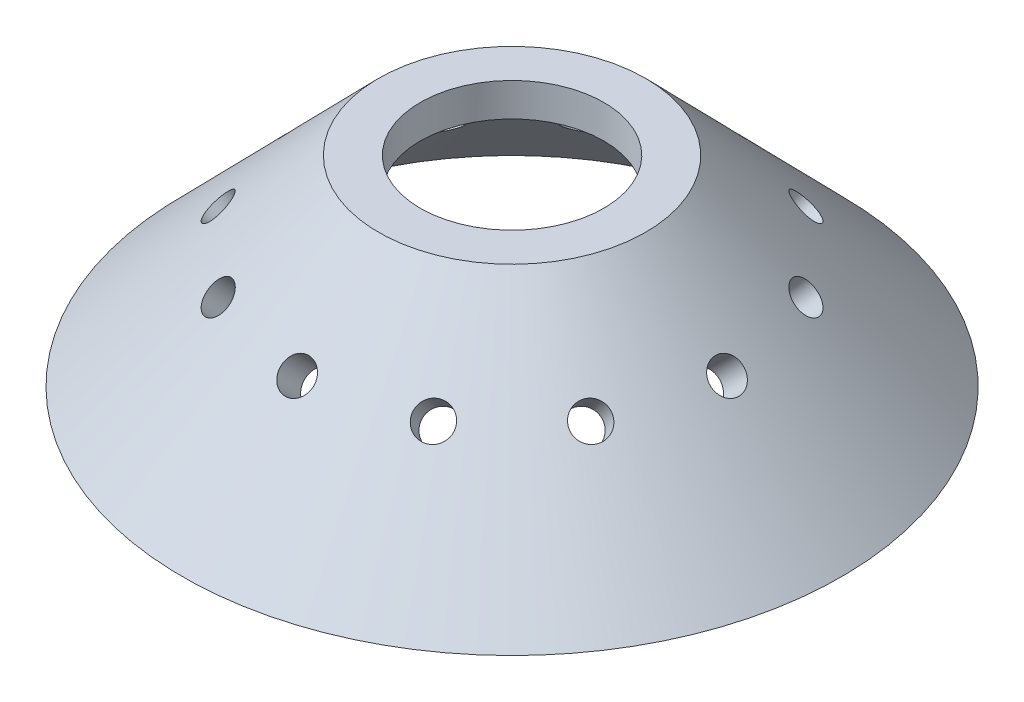
SolidWorks part; units mm, degrees
ref_plane "Front Plane" through (0, 0, 0) normal (0, 0, 1) x (1, 0, 0)
ref_plane "Top Plane" through (0, 0, 0) normal (0, 1, 0) x (1, 0, 0)
ref_plane "Right Plane" through (0, 0, 0) normal (1, 0, 0) x (0, 0, -1)
sketch "Sketch6" plane through (0, 0, 0) normal (0, 0, 1) x (1, 0, 0)
  line L2 (49.3939, -30) -> (20, 0)
  line L3 (20, 0) -> (0, 0)
  line L4 (49.3939, -30) -> (42.3939, -30)
  line L5 (42.3939, -30) -> (17.899, -5)
  line L6 (17.899, -5) -> (0, -5)
  line L7 (0, -5) -> (0, 0)
  line L8 (0, -5) -> (0, -30) construction
  line L9 (0, -30) -> (42.3939, -30) construction
  line L10 (49.3939, -30) -> (49.3939, -12.5) construction
  line L11 (49.3939, -12.5) -> (32.2474, -12.5) construction
  dimension "D2" = 5
  dimension "D3" = 20
  dimension "D1" = 5
  dimension "D4" = 7
  dimension "D5" = 30
  dimension "D6" = 17.5
revolve "Revolve2" add sketch "Sketch6" angle 360 about L7
ref_plane "Plane1" through (10.2041, 9.9979, 0) normal (0.7143, 0.6999, 0) x (0, 0, -1)
sketch "Sketch11" plane through (0, 0, 0) normal (0, 1, 0) x (1, 0, 0)
  line L0 (-20, 0) -> (20, 0) construction
  circle A0 centre (0, 0) radius 13.75
  circle A2 centre (0, 0) radius 20 construction
  dimension "D1" = 27.5
extrude "Cut-Extrude1" cut sketch "Sketch11" against normal through all contours A0
sketch "Sketch24" plane through (10.2041, 9.9979, 0) normal (0.7143, 0.6999, 0) x (0, 0, -1)
  circle A0 centre (0, -31.4971) radius 2.5
  dimension "D1" = 5
extrude "Cut-Extrude2" cut sketch "Sketch24" against normal through all contours A0
pattern_circular "CirPattern10" count 12 over 360 about axis through (0, -5, 0) along (0, -1, 0) of "Cut-Extrude2" reverse direction yes
equation "\"height\"= 3cm"
equation "\"D5@Sketch6\"=\"height\""
equation "\"D6@Sketch6\"=\"height\"/2 + 0.25"
